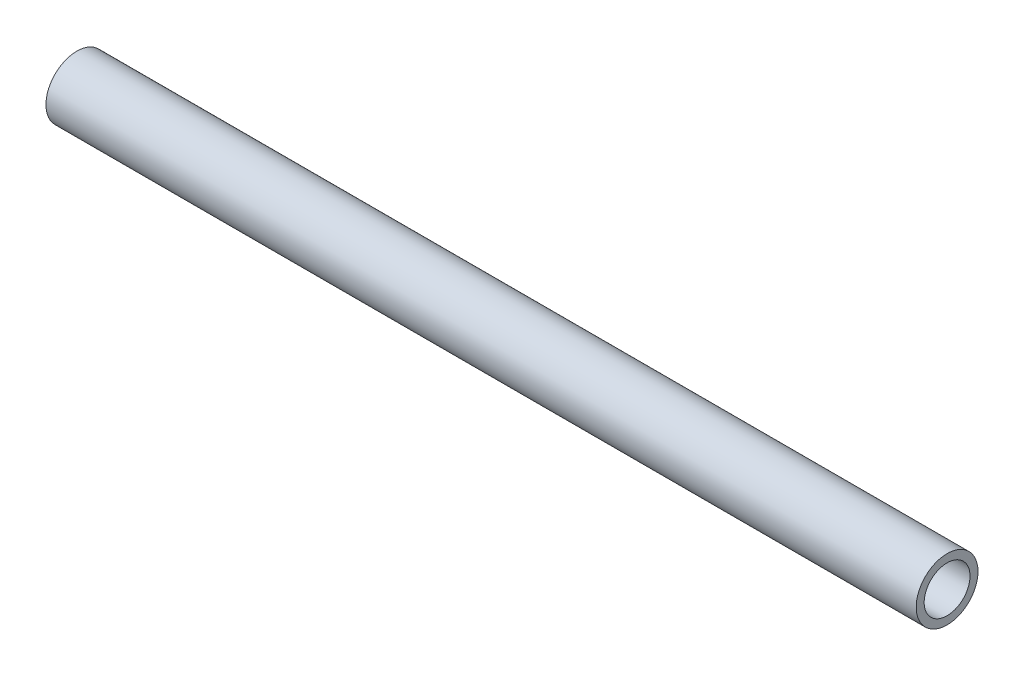
SolidWorks part; units mm, degrees
material "PVC Rígido"
ref_plane "Alzado" through (0, 0, 0) normal (0, 0, 1) x (1, 0, 0)
ref_plane "Planta" through (0, 0, 0) normal (0, 1, 0) x (1, 0, 0)
ref_plane "Vista lateral" through (0, 0, 0) normal (1, 0, 0) x (0, 0, -1)
sketch "Croquis1" plane through (0, 0, 0) normal (1, 0, 0) x (0, 0, -1)
  circle A0 centre (0, 0) radius 10.65
  circle A1 centre (0, 0) radius 7.9
  dimension "D1" = 21.3
  dimension "D2" = 15.8
extrude "Saliente-Extruir1" add sketch "Croquis1" along normal blind 300
